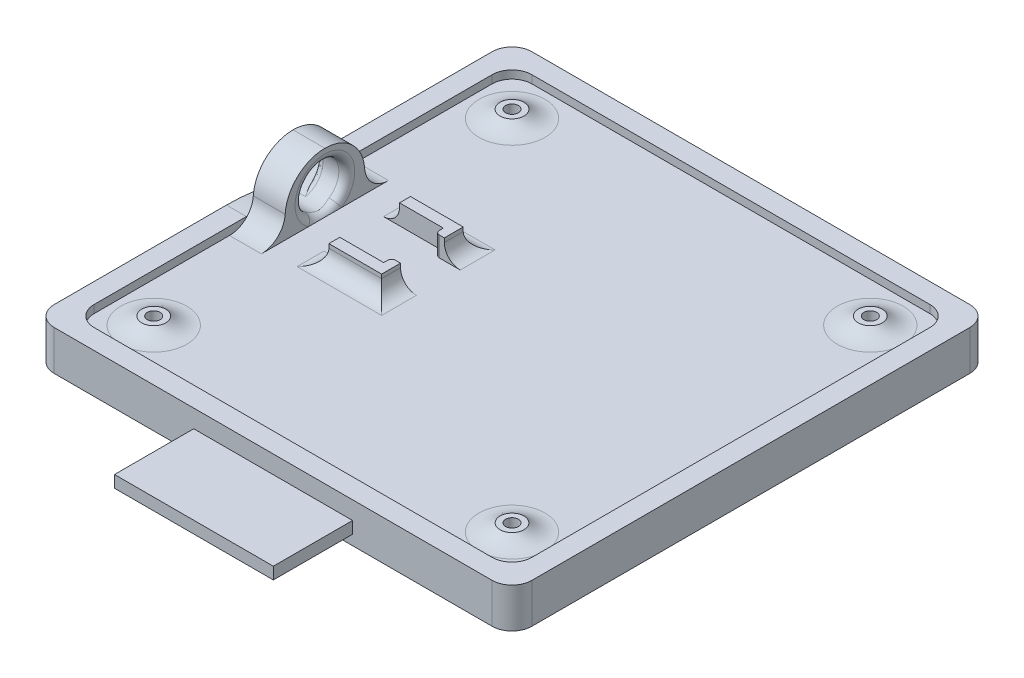
SolidWorks part; units mm, degrees
ref_plane "Front Plane" through (0, 0, 0) normal (0, 0, 1) x (1, 0, 0)
ref_plane "Top Plane" through (0, 0, 0) normal (0, 1, 0) x (1, 0, 0)
ref_plane "Right Plane" through (0, 0, 0) normal (1, 0, 0) x (0, 0, -1)
sketch "Sketch1" plane through (0, 0, 0) normal (0, 1, 0) x (1, 0, 0)
  line L1 (60, 60) -> (-60, 60)
  line L2 (60, 60) -> (60, -60)
  line L3 (60, -60) -> (-60, -60)
  line L4 (-60, 60) -> (-60, -60)
  line L5 (60, 60) -> (-60, -60) construction
  line L6 (60, -60) -> (-60, 60) construction
  point P0 (0, 0)
extrude "Boss-Extrude1" add sketch "Sketch1" along normal blind 10
sketch "Sketch2" plane through (0, 10, 0) normal (0, 1, 0) x (1, 0, 0)
  line L1 (55, 55) -> (-55, 55)
  line L2 (55, 55) -> (55, -55)
  line L3 (55, -55) -> (-55, -55)
  line L4 (-55, 55) -> (-55, -55)
  line L5 (55, 55) -> (-55, -55) construction
  line L6 (55, -55) -> (-55, 55) construction
  point P0 (0, 0)
extrude "Cut-Extrude1" cut sketch "Sketch2" against normal blind 2
sketch "Sketch3" plane through (0, 8, 0) normal (0, 1, 0) x (1, 0, 0)
  circle A0 centre (-45, 45) radius 3
extrude "Boss-Extrude2" add sketch "Sketch3" along normal blind 2
sketch "Sketch4" plane through (0, 8, 0) normal (0, 1, 0) x (1, 0, 0)
  circle A0 centre (-45, -45) radius 3
extrude "Boss-Extrude3" add sketch "Sketch4" along normal blind 2
sketch "Sketch5" plane through (0, 8, 0) normal (0, 1, 0) x (1, 0, 0)
  circle A0 centre (45, 45) radius 3
extrude "Boss-Extrude4" add sketch "Sketch5" along normal blind 2
sketch "Sketch6" plane through (0, 8, 0) normal (0, 1, 0) x (1, 0, 0)
  circle A0 centre (45, -45) radius 3
extrude "Boss-Extrude5" add sketch "Sketch6" along normal blind 2
sketch "Sketch7" plane through (0, 10, 0) normal (0, 1, 0) x (1, 0, 0)
  circle A0 centre (-45, 45) radius 1.6
extrude "Cut-Extrude2" cut sketch "Sketch7" against normal blind 3.65
sketch "Sketch8" plane through (0, 10, 0) normal (0, 1, 0) x (1, 0, 0)
  circle A0 centre (45, 45) radius 1.6
extrude "Cut-Extrude3" cut sketch "Sketch8" against normal blind 3.65
sketch "Sketch9" plane through (0, 10, 0) normal (0, 1, 0) x (1, 0, 0)
  circle A0 centre (-45, -45) radius 1.6
extrude "Cut-Extrude4" cut sketch "Sketch9" against normal blind 3.65
sketch "Sketch10" plane through (0, 10, 0) normal (0, 1, 0) x (1, 0, 0)
  circle A0 centre (45, -45) radius 1.6
extrude "Cut-Extrude5" cut sketch "Sketch10" against normal blind 3.65
sketch "Sketch12" plane through (0, 0, 60) normal (0, 0, 1) x (1, 0, 0)
  line L1 (-19.95, 5.5) -> (19.95, 5.5)
  line L2 (-19.95, 5.5) -> (-19.95, 2.5)
  line L3 (-19.95, 2.5) -> (19.95, 2.5)
  line L4 (19.95, 5.5) -> (19.95, 2.5)
extrude "Boss-Extrude6" add sketch "Sketch12" along normal blind 19.9
fillet "Fillet1" radius 5 1 edges at (-55, 9, -55)
fillet "Fillet2" radius 5 2 edges at (55, 9, 55) (55, 9, -55)
fillet "Fillet3" radius 5 1 edges at (-55, 9, 55)
fillet "Fillet4" radius 8 4 edges at (45, 8, -48) (45, 8, 42) (-45, 8, 42) (-45, 8, -48)
fillet "Fillet5" radius 5 2 edges at (60, 5, 60) (60, 5, -60)
fillet "Fillet6" radius 5 2 edges at (-60, 5, 60) (-60, 5, -60)
sketch "Sketch14" plane through (0, 8, 0) normal (0, 1, 0) x (1, 0, 0)
  line L1 (-55, 10) -> (-47, 10)
  line L2 (-55, 10) -> (-55, -10)
  line L3 (-55, -10) -> (-47, -10)
  line L4 (-47, 10) -> (-47, -10)
extrude "Boss-Extrude8" add sketch "Sketch14" along normal blind 15
sketch "Sketch16" plane through (-47, 0, 0) normal (1, 0, 0) x (0, 0, -1)
  circle A0 centre (0, 14.25) radius 5.5
extrude "Cut-Extrude8" cut sketch "Sketch16" against normal through all
fillet "Fillet10" radius 50 2 edges at (-57.5, 10, -3.4911) (-57.5, 10, 3.4911)
fillet "Fillet11" radius 2 1 edges at (-55, 19.75, 0)
fillet "Fillet12" radius 2 1 edges at (-47, 14.25, -5.5)
fillet "Fillet13" radius 10 2 edges at (-51, 23, -10) (-51, 23, 10)
fillet "Fillet15" radius 6 2 edges at (-51, 8, -10) (-51, 8, 10)
sketch "Sketch18" plane through (0, 8, 0) normal (0, 1, 0) x (1, 0, 0)
  line L1 (-24.75, 7.5) -> (-35.75, 7.5)
  line L2 (-24.75, 7.5) -> (-24.75, 10.25)
  line L3 (-24.75, 10.25) -> (-35.75, 10.25)
  line L4 (-35.75, 7.5) -> (-35.75, 10.25)
  point P4 (0, 0)
  point P5 (0, 0)
extrude "Boss-Extrude9" add sketch "Sketch18" along normal blind 5
sketch "Sketch20" plane through (0, 8, 0) normal (0, 1, 0) x (1, 0, 0)
  line L1 (-24.75, 10.25) -> (-22.5, 10.25)
  line L2 (-24.75, 10.25) -> (-24.75, 5.5)
  line L3 (-24.75, 5.5) -> (-22.5, 5.5)
  line L4 (-22.5, 10.25) -> (-22.5, 5.5)
extrude "Boss-Extrude10" add sketch "Sketch20" along normal blind 5
sketch "Sketch21" plane through (0, 8, 0) normal (0, 1, 0) x (1, 0, 0)
  line L1 (-24.75, -7.5) -> (-35.75, -7.5)
  line L2 (-24.75, -7.5) -> (-24.75, -10.25)
  line L3 (-24.75, -10.25) -> (-35.75, -10.25)
  line L4 (-35.75, -7.5) -> (-35.75, -10.25)
extrude "Boss-Extrude11" add sketch "Sketch21" along normal blind 5
sketch "Sketch22" plane through (0, 8, 0) normal (0, 1, 0) x (1, 0, 0)
  line L1 (-24.75, -10.25) -> (-22.5, -10.25)
  line L2 (-24.75, -10.25) -> (-24.75, -5.5)
  line L3 (-24.75, -5.5) -> (-22.5, -5.5)
  line L4 (-22.5, -10.25) -> (-22.5, -5.5)
extrude "Boss-Extrude12" add sketch "Sketch22" along normal blind 5
fillet "Fillet16" radius 4 2 edges at (-29.125, 8, -10.25) (-29.125, 8, 10.25)
fillet "Fillet17" radius 4 2 edges at (-22.5, 8, -9.875) (-22.5, 8, 9.875)
fillet "Fillet18" radius 4 2 edges at (-35.75, 8, 10.875) (-35.75, 8, -10.875)
fillet "Fillet19" radius 1 1 edges at (-24.75, 10.5, -5.5)
fillet "Fillet20" radius 1 1 edges at (-24.75, 10.5, 5.5)
